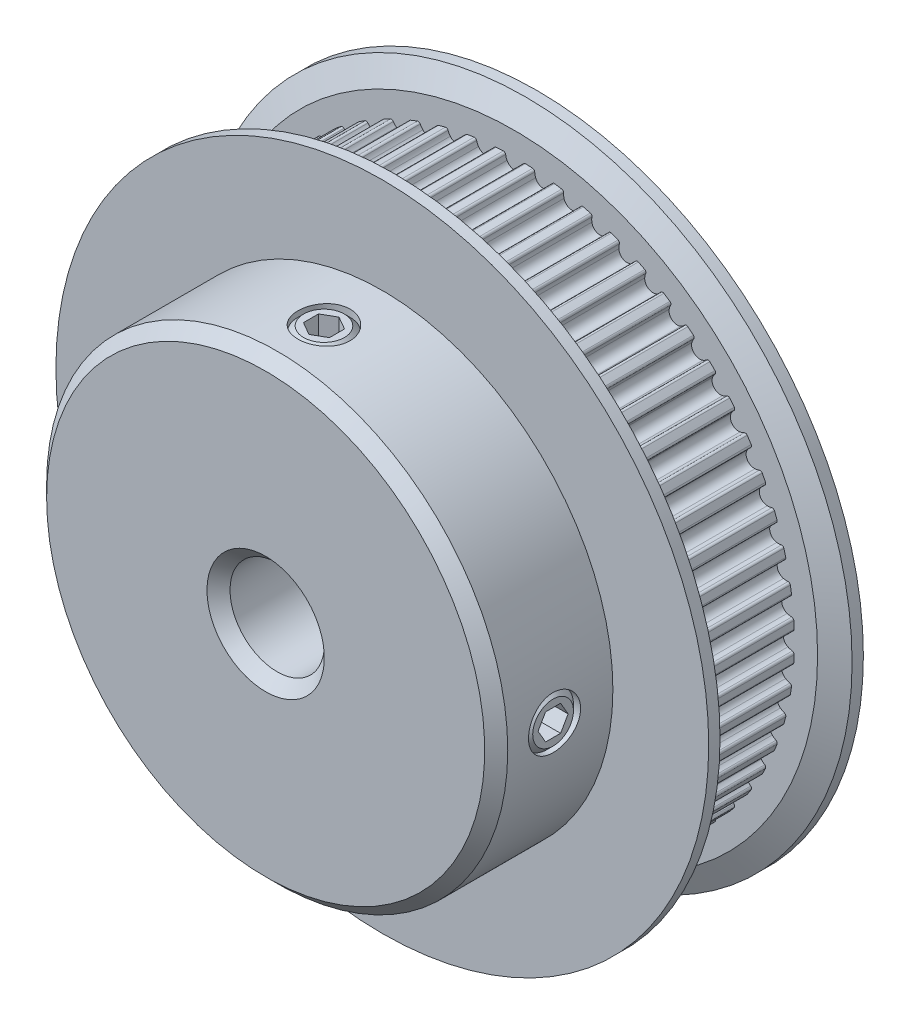
SolidWorks part; units mm, degrees
ref_plane "Front Plane" through (0, 0, 0) normal (0, 0, 1) x (1, 0, 0)
ref_plane "Top Plane" through (0, 0, 0) normal (0, 1, 0) x (1, 0, 0)
ref_plane "Right Plane" through (0, 0, 0) normal (1, 0, 0) x (0, 0, -1)
sketch "Sketch1" plane through (0, 0, 0) normal (0, 0, 1) x (1, 0, 0)
  line L1 (-1.9027, 18.097) -> (1.9027, 18.097) construction
  line L4 (0, 0) -> (0, 18.097) construction
  line L5 (0, 18.097) -> (0, 19.6762) construction
  line L6 (0, 19.101) -> (1.9973, 18.9963) construction
  line L7 (1.9973, 18.9963) -> (2.8966, 18.9017) construction
  line L8 (1.9973, 18.9963) -> (1.9027, 18.097) construction
  line L9 (-1.9973, 18.9963) -> (-1.9027, 18.097) construction
  line L10 (-1.9707, 18.7437) -> (-2.31, 21.971)
  line L11 (-2.31, 21.971) -> (2.31, 21.971)
  line L12 (2.31, 21.971) -> (1.9707, 18.7437)
  circle A0 centre (0, 0) radius 19.101 construction
  circle A1 centre (0, 0) radius 21.971 construction
  circle A2 centre (0, 0) radius 18.847 construction
  arc A3 (-0.4989, 18.4088) -> (0.4989, 18.4088) centre (0, 18.652) ccw
  arc A4 (-0.4989, 18.4088) -> (-0.5897, 18.7039) centre (0.4, 18.847) cw
  arc A5 (-1.9707, 18.7437) -> (-0.7441, 18.8323) centre (0, 0) cw
  arc A6 (-0.5897, 18.7039) -> (-0.7441, 18.8323) centre (-0.7382, 18.6824) ccw
  arc A7 (1.9707, 18.7437) -> (0.7441, 18.8323) centre (0, 0) ccw
  arc A8 (0.5897, 18.7039) -> (0.7441, 18.8323) centre (0.7382, 18.6824) cw
  arc A9 (0.4989, 18.4088) -> (0.5897, 18.7039) centre (-0.4, 18.847) ccw
  point P6 (0, 20.9083)
  point P11 (0, 19.101)
  point P13 (0, 21.971)
  point P14 (0, 18.847)
  dimension "D1" = 1.2321
  dimension "D2" = 0.5752
sketch "Sketch2" plane through (0, 0, 0) normal (1, 0, 0) x (0, 0, -1)
  line L0 (-9.1313, 3.175) -> (9.1313, 3.175)
  line L1 (-9.1313, 3.175) -> (-9.1313, 15.52)
  line L2 (-9.1313, 15.52) -> (-1.2787, 15.52)
  line L3 (-1.2787, 15.52) -> (-1.2787, 21.971)
  line L4 (-1.2787, 21.971) -> (0.2413, 21.971) construction
  line L5 (0.2413, 21.971) -> (0.2413, 18.847) construction
  line L6 (0.2413, 18.847) -> (7.6113, 18.847)
  line L7 (7.6113, 18.847) -> (7.6113, 21.971) construction
  line L8 (7.6113, 21.971) -> (9.1313, 21.971) construction
  line L9 (9.1313, 21.971) -> (9.1313, 3.175)
  line L10 (-9.1313, 0) -> (9.1313, 0) construction
  line L11 (8.3713, 21.971) -> (7.6113, 20.409)
  line L12 (0.2413, 20.409) -> (-0.5187, 21.971)
  line L13 (-1.2787, 21.971) -> (-0.5187, 21.971)
  line L14 (0.2413, 20.409) -> (0.2413, 18.847)
  line L15 (7.6113, 18.847) -> (7.6113, 20.409)
  line L16 (8.3713, 21.971) -> (9.1313, 21.971)
  arc A0 (0.2413, 20.409) -> (-0.5187, 21.971) centre (-1.7439, 20.409) ccw construction
  arc A1 (7.6113, 20.409) -> (8.3713, 21.971) centre (9.5965, 20.409) cw construction
  point P12 (0.2413, 20.409)
  point P14 (-0.5187, 21.971)
  point P20 (7.6113, 20.409)
  point P21 (8.3713, 21.971)
  point P25 (7.6113, 0)
  point P26 (0.2413, 0)
revolve "Revolve1" add sketch "Sketch2" angle 360 mid plane about L10
sketch "Sketch3" plane through (0, 0, 0) normal (0, 0, 1) x (1, 0, 0)
  line L6 (2.31, 21.971) -> (-2.31, 21.971)
  line L7 (1.9707, 18.7437) -> (2.31, 21.971)
  line L8 (-2.31, 21.971) -> (-1.9707, 18.7437)
  line L9 (2.31, 21.971) -> (-2.31, 21.971)
  line L10 (1.9707, 18.7437) -> (2.31, 21.971)
  line L11 (-2.31, 21.971) -> (-1.9707, 18.7437)
  arc A8 (1.9707, 18.7437) -> (0.7441, 18.8323) centre (0, 0) ccw
  arc A9 (0.7441, 18.8323) -> (0.5897, 18.7039) centre (0.7382, 18.6824) ccw
  arc A10 (0.4989, 18.4088) -> (0.5897, 18.7039) centre (-0.4, 18.847) ccw
  arc A11 (-0.4989, 18.4088) -> (0.4989, 18.4088) centre (0, 18.652) ccw
  arc A12 (-0.5897, 18.7039) -> (-0.4989, 18.4088) centre (0.4, 18.847) ccw
  arc A13 (-0.5897, 18.7039) -> (-0.7441, 18.8323) centre (-0.7382, 18.6824) ccw
  arc A14 (-0.7441, 18.8323) -> (-1.9707, 18.7437) centre (0, 0) ccw
  arc A15 (1.9707, 18.7437) -> (0.7441, 18.8323) centre (0, 0) ccw
  arc A16 (0.7441, 18.8323) -> (0.5897, 18.7039) centre (0.7382, 18.6824) ccw
  arc A17 (0.4989, 18.4088) -> (0.5897, 18.7039) centre (-0.4, 18.847) ccw
  arc A18 (-0.4989, 18.4088) -> (0.4989, 18.4088) centre (0, 18.652) ccw
  arc A19 (-0.5897, 18.7039) -> (-0.4989, 18.4088) centre (0.4, 18.847) ccw
  arc A20 (-0.5897, 18.7039) -> (-0.7441, 18.8323) centre (-0.7382, 18.6824) ccw
  arc A21 (-0.7441, 18.8323) -> (-1.9707, 18.7437) centre (0, 0) ccw
  dimension "D1" = 0
extrude "Cut-Extrude1" cut sketch "Sketch3" against normal up to vertex (7.6113 mm away) from vertex up to point (0, 18.847, -7.6113) starting at point (0, 18.847, -0.2413)
pattern_circular "CirPattern1" count 60 over 360 about axis through (0, 0, 9.1313) along (0, 0, 1) of "Cut-Extrude1"
sketch "Sketch4" plane through (0, 0, 0) normal (1, 0, 0) x (0, -1, 0)
  line L0 (0, -1.2787) -> (0, -9.1313) construction
  line L1 (-15.52, -1.2787) -> (15.52, -1.2787) construction
  line L2 (-15.52, -9.1313) -> (15.52, -9.1313) construction
  circle A0 centre (0, -5.205) radius 1.7526
extrude "Cut-Extrude2" cut sketch "Sketch4" along normal through all
ref_plane "Plane1" through (0, 0, 5.205) normal (0, 0, 1) x (1, 0, 0)
sketch "Sketch5" plane through (0, 0, 5.205) normal (0, 0, 1) x (1, 0, 0)
  line L0 (0, 0.1664) -> (0, 15.52) construction
  line L1 (3.175, -1.3716) -> (3.175, 0)
  line L2 (3.556, -1.7526) -> (15.0397, -1.7526)
  line L3 (3.175, 0) -> (15.52, 0) construction
  line L4 (3.175, 0) -> (15.4207, 0)
  line L5 (15.4207, 0) -> (15.4207, -1.3716)
  line L6 (3.556, -1.7526) -> (3.175, -1.3716)
  line L7 (15.4207, -1.3716) -> (15.0397, -1.7526)
  circle A0 centre (0, 0) radius 15.52 construction
  circle A1 centre (0, 0) radius 3.175 construction
  point P2 (3.175, -1.7526)
  point P11 (15.4207, -1.7526)
revolve "Revolve2" add sketch "Sketch5" angle 360 mid plane about L4
sketch "Sketch6" plane through (15.4207, 5.3841, 0) normal (-1, 0, 0) x (0, -1, 0)
  line L1 (5.3841, 6.2169) -> (4.5078, 5.7109)
  line L2 (4.5078, 5.7109) -> (4.5078, 4.6991)
  line L3 (4.5078, 4.6991) -> (5.3841, 4.1931)
  line L4 (5.3841, 4.1931) -> (6.2604, 4.6991)
  line L5 (6.2604, 4.6991) -> (6.2604, 5.7109)
  line L6 (6.2604, 5.7109) -> (5.3841, 6.2169)
  circle A0 centre (5.3841, 5.205) radius 0.8763 construction
  dimension "D1" = 1.7526
extrude "Cut-Extrude3" cut sketch "Sketch6" along normal blind 1.3144
pattern_circular "CirPattern2" count 2 over 90 about axis through (0, 0, 9.1313) along (0, 0, 1) of "Cut-Extrude2", "Revolve2", "Cut-Extrude3"
chamfer "Chamfer1" distance 0.776 angle 45 2 edges at (3.175, 0, 9.1313) (15.52, 0, 9.1313)
ref_axis "Center Axis 1" through (0, 0, -9.1313) along (0, 0, 1)
ref_plane "Contact Plane 1" through (0, 0, 9.1313) normal (0, 0, 1) x (1, 0, 0)
ref_plane "Contact Plane 2" through (0, 0, -9.1313) normal (0, 0, -1) x (-1, 0, 0)
equation "\"D2@Sketch1\" = \"D1@Sketch1\"/2"
equation "\"D1@Sketch6\" = \"Set Screw@Sketch4\" / 2"
equation "\"D1@Cut-Extrude3\" = \"D1@Sketch6\"*.75"
equation "\"D1@Chamfer1\"=\"Hub Dia@Sketch2\"*.025"
